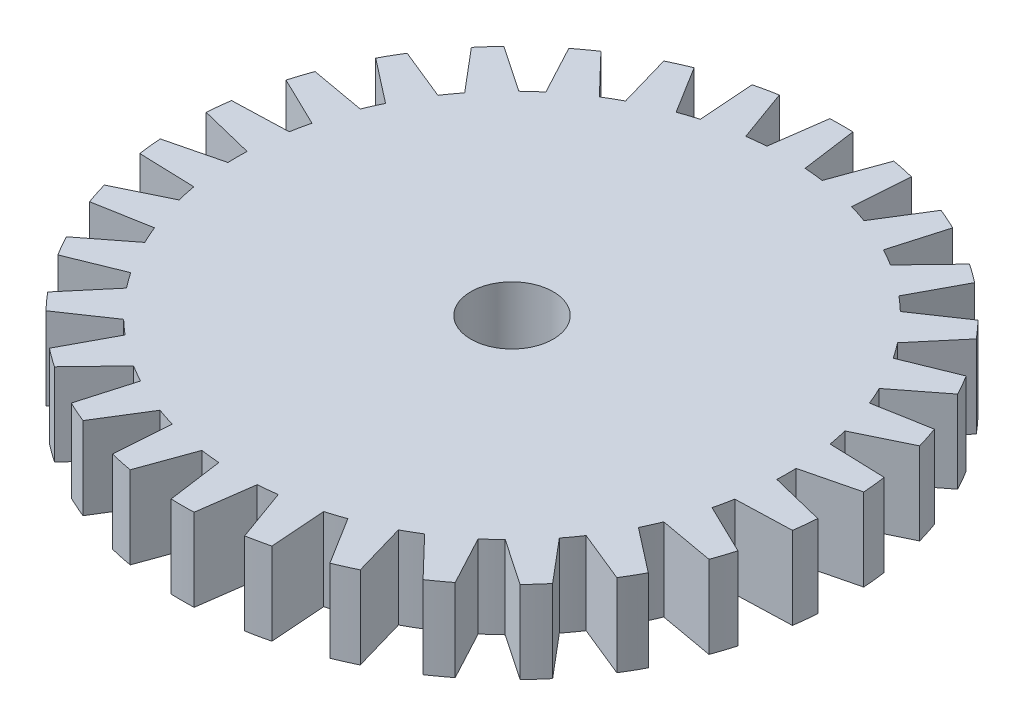
SolidWorks part; units mm, degrees
ref_plane "Front Plane" through (0, 0, 0) normal (0, 0, 1) x (1, 0, 0)
ref_plane "Top Plane" through (0, 0, 0) normal (0, 1, 0) x (1, 0, 0)
ref_plane "Right Plane" through (0, 0, 0) normal (1, 0, 0) x (0, 0, -1)
sketch "Sketch1" plane through (0, 0, 0) normal (0, 1, 0) x (1, 0, 0)
  line L0 (-2.0313, -0.0066) -> (-2.0313, 11.9934) construction
  line L1 (-2.0313, -0.0066) -> (-2.4501, 11.9861) construction
  line L2 (-2.0313, -0.0066) -> (-2.7289, 9.969) construction
  line L3 (-2.0313, -0.0066) -> (-3.0766, 9.9386) construction
  line L4 (-2.4501, 11.9861) -> (-2.7289, 9.969)
  line L5 (-1.6125, 11.9861) -> (-1.3338, 9.969)
  line L6 (0.0525, 11.8111) -> (-0.6396, 9.8961)
  line L7 (0.8717, 11.6369) -> (0.7251, 9.606)
  line L8 (2.464, 11.1196) -> (1.3889, 9.3903)
  line L9 (3.2291, 10.7789) -> (2.6634, 8.8229)
  line L10 (4.679, 9.9418) -> (3.2679, 8.4739)
  line L11 (5.3566, 9.4495) -> (4.3966, 7.6538)
  line L12 (6.6008, 8.3293) -> (4.9153, 7.1868)
  line L13 (7.1612, 7.7068) -> (5.8488, 6.15)
  line L14 (8.1453, 6.3524) -> (6.2591, 5.5853)
  line L15 (8.5641, 5.6271) -> (6.9566, 4.3771)
  line L16 (9.245, 4.0976) -> (7.2405, 3.7395)
  line L17 (9.5038, 3.301) -> (7.6716, 2.4126)
  line L18 (9.8519, 1.6635) -> (7.8168, 1.7299)
  line L19 (9.9395, 0.8305) -> (7.9626, 0.3424)
  line L20 (9.9395, -0.8437) -> (7.9626, -0.3556)
  line L21 (9.8519, -1.6767) -> (7.8168, -1.7431)
  line L22 (9.5038, -3.3143) -> (7.6716, -2.4258)
  line L23 (9.245, -4.1108) -> (7.2405, -3.7527)
  line L24 (8.5641, -5.6403) -> (6.9566, -4.3903)
  line L25 (8.1453, -6.3656) -> (6.2591, -5.5985)
  line L26 (7.1612, -7.7201) -> (5.8488, -6.1632)
  line L27 (6.6008, -8.3425) -> (4.9153, -7.2)
  line L28 (5.3566, -9.4627) -> (4.3966, -7.667)
  line L29 (4.679, -9.9551) -> (3.2679, -8.4871)
  line L30 (3.2291, -10.7921) -> (2.6634, -8.8361)
  line L31 (2.464, -11.1328) -> (1.3889, -9.4035)
  line L32 (0.8717, -11.6502) -> (0.7251, -9.6192)
  line L33 (0.0525, -11.8243) -> (-0.6396, -9.9093)
  line L34 (-1.6125, -11.9993) -> (-1.3338, -9.9822)
  line L35 (-2.4501, -11.9993) -> (-2.7289, -9.9822)
  line L36 (-4.1151, -11.8243) -> (-3.423, -9.9093)
  line L37 (-4.9344, -11.6502) -> (-4.7877, -9.6192)
  line L38 (-6.5266, -11.1328) -> (-5.4515, -9.4035)
  line L39 (-7.2918, -10.7921) -> (-6.726, -8.8361)
  line L40 (-8.7416, -9.9551) -> (-7.3305, -8.4871)
  line L41 (-9.4193, -9.4627) -> (-8.4592, -7.667)
  line L42 (-10.6634, -8.3425) -> (-8.9779, -7.2)
  line L43 (-11.2239, -7.7201) -> (-9.9114, -6.1632)
  line L44 (-12.2079, -6.3656) -> (-10.3217, -5.5985)
  line L45 (-12.6267, -5.6403) -> (-11.0193, -4.3903)
  line L46 (-13.3076, -4.1108) -> (-11.3032, -3.7527)
  line L47 (-13.5665, -3.3143) -> (-11.7343, -2.4258)
  line L48 (-13.9145, -1.6767) -> (-11.8794, -1.7431)
  line L49 (-14.0021, -0.8437) -> (-12.0252, -0.3556)
  line L50 (-14.0021, 0.8305) -> (-12.0252, 0.3424)
  line L51 (-13.9145, 1.6635) -> (-11.8794, 1.7299)
  line L52 (-13.5665, 3.301) -> (-11.7343, 2.4126)
  line L53 (-13.3076, 4.0976) -> (-11.3032, 3.7395)
  line L54 (-12.6267, 5.6271) -> (-11.0193, 4.3771)
  line L55 (-12.2079, 6.3524) -> (-10.3217, 5.5853)
  line L56 (-11.2239, 7.7068) -> (-9.9114, 6.15)
  line L57 (-10.6634, 8.3293) -> (-8.9779, 7.1868)
  line L58 (-9.4193, 9.4495) -> (-8.4592, 7.6538)
  line L59 (-8.7416, 9.9418) -> (-7.3305, 8.4739)
  line L60 (-7.2918, 10.7789) -> (-6.726, 8.8229)
  line L61 (-6.5266, 11.1196) -> (-5.4515, 9.3903)
  line L62 (-4.9344, 11.6369) -> (-4.7877, 9.606)
  line L63 (-4.1151, 11.8111) -> (-3.423, 9.8961)
  arc A0 (-1.6125, 11.9861) -> (-2.4501, 11.9861) centre (-2.0313, -0.0066) ccw
  arc A1 (-2.7289, 9.969) -> (-3.423, 9.8961) centre (-2.0313, -0.0066) ccw
  arc A2 (-0.6396, 9.8961) -> (-1.3338, 9.969) centre (-2.0313, -0.0066) ccw
  arc A3 (1.3889, 9.3903) -> (0.7251, 9.606) centre (-2.0313, -0.0066) ccw
  arc A4 (0.8717, 11.6369) -> (0.0525, 11.8111) centre (-2.0313, -0.0066) ccw
  arc A5 (3.2679, 8.4739) -> (2.6634, 8.8229) centre (-2.0313, -0.0066) ccw
  arc A6 (4.9153, 7.1868) -> (4.3966, 7.6538) centre (-2.0313, -0.0066) ccw
  arc A7 (6.2591, 5.5853) -> (5.8488, 6.15) centre (-2.0313, -0.0066) ccw
  arc A8 (7.2405, 3.7395) -> (6.9566, 4.3771) centre (-2.0313, -0.0066) ccw
  arc A9 (7.8168, 1.7299) -> (7.6716, 2.4126) centre (-2.0313, -0.0066) ccw
  arc A10 (7.9626, -0.3556) -> (7.9626, 0.3424) centre (-2.0313, -0.0066) ccw
  arc A11 (7.6716, -2.4258) -> (7.8168, -1.7431) centre (-2.0313, -0.0066) ccw
  arc A12 (6.9566, -4.3903) -> (7.2405, -3.7527) centre (-2.0313, -0.0066) ccw
  arc A13 (5.8488, -6.1632) -> (6.2591, -5.5985) centre (-2.0313, -0.0066) ccw
  arc A14 (4.3966, -7.667) -> (4.9153, -7.2) centre (-2.0313, -0.0066) ccw
  arc A15 (2.6634, -8.8361) -> (3.2679, -8.4871) centre (-2.0313, -0.0066) ccw
  arc A16 (0.7251, -9.6192) -> (1.3889, -9.4035) centre (-2.0313, -0.0066) ccw
  arc A17 (-1.3338, -9.9822) -> (-0.6396, -9.9093) centre (-2.0313, -0.0066) ccw
  arc A18 (-3.423, -9.9093) -> (-2.7289, -9.9822) centre (-2.0313, -0.0066) ccw
  arc A19 (-5.4515, -9.4035) -> (-4.7877, -9.6192) centre (-2.0313, -0.0066) ccw
  arc A20 (-7.3305, -8.4871) -> (-6.726, -8.8361) centre (-2.0313, -0.0066) ccw
  arc A21 (-8.9779, -7.2) -> (-8.4592, -7.667) centre (-2.0313, -0.0066) ccw
  arc A22 (-10.3217, -5.5985) -> (-9.9114, -6.1632) centre (-2.0313, -0.0066) ccw
  arc A23 (-11.3032, -3.7527) -> (-11.0193, -4.3903) centre (-2.0313, -0.0066) ccw
  arc A24 (-11.8794, -1.7431) -> (-11.7343, -2.4258) centre (-2.0313, -0.0066) ccw
  arc A25 (-12.0252, 0.3424) -> (-12.0252, -0.3556) centre (-2.0313, -0.0066) ccw
  arc A26 (-11.7343, 2.4126) -> (-11.8794, 1.7299) centre (-2.0313, -0.0066) ccw
  arc A27 (-11.0193, 4.3771) -> (-11.3032, 3.7395) centre (-2.0313, -0.0066) ccw
  arc A28 (-9.9114, 6.15) -> (-10.3217, 5.5853) centre (-2.0313, -0.0066) ccw
  arc A29 (-8.4592, 7.6538) -> (-8.9779, 7.1868) centre (-2.0313, -0.0066) ccw
  arc A30 (-6.726, 8.8229) -> (-7.3305, 8.4739) centre (-2.0313, -0.0066) ccw
  arc A31 (-4.7877, 9.606) -> (-5.4515, 9.3903) centre (-2.0313, -0.0066) ccw
  arc A32 (3.2291, 10.7789) -> (2.464, 11.1196) centre (-2.0313, -0.0066) ccw
  arc A33 (5.3566, 9.4495) -> (4.679, 9.9418) centre (-2.0313, -0.0066) ccw
  arc A34 (7.1612, 7.7068) -> (6.6008, 8.3293) centre (-2.0313, -0.0066) ccw
  arc A35 (8.5641, 5.6271) -> (8.1453, 6.3524) centre (-2.0313, -0.0066) ccw
  arc A36 (9.5038, 3.301) -> (9.245, 4.0976) centre (-2.0313, -0.0066) ccw
  arc A37 (9.9395, 0.8305) -> (9.8519, 1.6635) centre (-2.0313, -0.0066) ccw
  arc A38 (9.8519, -1.6767) -> (9.9395, -0.8437) centre (-2.0313, -0.0066) ccw
  arc A39 (9.245, -4.1108) -> (9.5038, -3.3143) centre (-2.0313, -0.0066) ccw
  arc A40 (8.1453, -6.3656) -> (8.5641, -5.6403) centre (-2.0313, -0.0066) ccw
  arc A41 (6.6008, -8.3425) -> (7.1612, -7.7201) centre (-2.0313, -0.0066) ccw
  arc A42 (4.679, -9.9551) -> (5.3566, -9.4627) centre (-2.0313, -0.0066) ccw
  arc A43 (2.464, -11.1328) -> (3.2291, -10.7921) centre (-2.0313, -0.0066) ccw
  arc A44 (0.0525, -11.8243) -> (0.8717, -11.6502) centre (-2.0313, -0.0066) ccw
  arc A45 (-2.4501, -11.9993) -> (-1.6125, -11.9993) centre (-2.0313, -0.0066) ccw
  arc A46 (-4.9344, -11.6502) -> (-4.1151, -11.8243) centre (-2.0313, -0.0066) ccw
  arc A47 (-7.2918, -10.7921) -> (-6.5266, -11.1328) centre (-2.0313, -0.0066) ccw
  arc A48 (-9.4193, -9.4627) -> (-8.7416, -9.9551) centre (-2.0313, -0.0066) ccw
  arc A49 (-11.2239, -7.7201) -> (-10.6634, -8.3425) centre (-2.0313, -0.0066) ccw
  arc A50 (-12.6267, -5.6403) -> (-12.2079, -6.3656) centre (-2.0313, -0.0066) ccw
  arc A51 (-13.5665, -3.3143) -> (-13.3076, -4.1108) centre (-2.0313, -0.0066) ccw
  arc A52 (-14.0021, -0.8437) -> (-13.9145, -1.6767) centre (-2.0313, -0.0066) ccw
  arc A53 (-13.9145, 1.6635) -> (-14.0021, 0.8305) centre (-2.0313, -0.0066) ccw
  arc A54 (-13.3076, 4.0976) -> (-13.5665, 3.301) centre (-2.0313, -0.0066) ccw
  arc A55 (-12.2079, 6.3524) -> (-12.6267, 5.6271) centre (-2.0313, -0.0066) ccw
  arc A56 (-10.6634, 8.3293) -> (-11.2239, 7.7068) centre (-2.0313, -0.0066) ccw
  arc A57 (-8.7416, 9.9418) -> (-9.4193, 9.4495) centre (-2.0313, -0.0066) ccw
  arc A58 (-6.5266, 11.1196) -> (-7.2918, 10.7789) centre (-2.0313, -0.0066) ccw
  arc A59 (-4.1151, 11.8111) -> (-4.9344, 11.6369) centre (-2.0313, -0.0066) ccw
  point P123 (-2.0313, -0.0066)
  point P124 (0, 0)
  dimension "D1" = 2
  dimension "D2" = 2
  dimension "D3" = 2
extrude "Boss-Extrude1" add sketch "Sketch1" along normal blind 3
sketch "Sketch2" plane through (0, 3, 0) normal (0, 1, 0) x (1, 0, 0)
  circle A0 centre (-2.0313, -0.0066) radius 1.5
extrude "Cut-Extrude1" cut sketch "Sketch2" against normal through all
